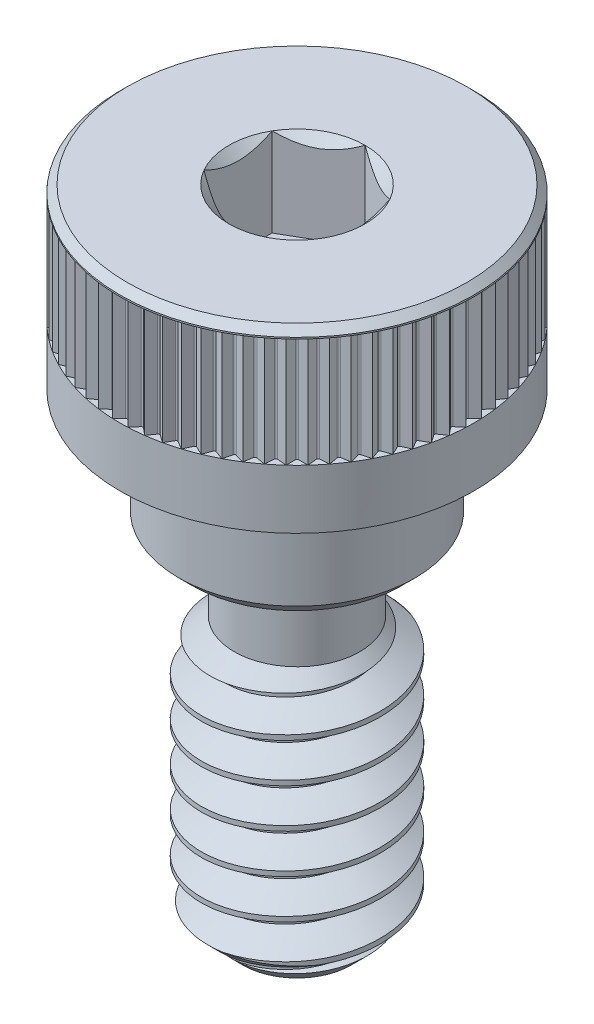
SolidWorks part; units mm, degrees
ref_plane "Front" through (0, 0, 0) normal (0, 0, 1) x (1, 0, 0)
ref_plane "Top" through (0, 0, 0) normal (0, 1, 0) x (1, 0, 0)
ref_plane "Right" through (0, 0, 0) normal (1, 0, 0) x (0, 0, -1)
sketch "Sketch1" plane through (0, 0, 0) normal (0, 1, 0) x (1, 0, 0)
  circle A0 centre (0, 0) radius 4.7625
  point P3 (0, -4.7625)
  dimension "Head Dia" = 9.525
extrude "Extrude1" add sketch "Sketch1" along normal blind 4.7625
sketch "Sketch2" plane through (0, 4.7625, 0) normal (0, 1, 0) x (-1, 0, 0)
  line L1 (0, -1.8331) -> (1.5875, -0.9165)
  line L2 (1.5875, -0.9165) -> (1.5875, 0.9165)
  line L3 (1.5875, 0.9165) -> (0, 1.8331)
  line L4 (0, 1.8331) -> (-1.5875, 0.9165)
  line L5 (-1.5875, 0.9165) -> (-1.5875, -0.9165)
  line L6 (-1.5875, -0.9165) -> (0, -1.8331)
  circle A0 centre (0, 0) radius 1.5875 construction
  circle A1 centre (0, 0) radius 4.7625 construction
  dimension "Hex Key" = 3.175
extrude "Cut-Extrude1" cut sketch "Sketch2" against normal blind 2.3813
sketch "Sketch4" plane through (0, 0, 0) normal (0, -1, 0) x (1, 0, 0)
  circle A0 centre (0, 0) radius 3.175
  circle A1 centre (0, 0) radius 4.7625 construction
  dimension "Shoulder Dia" = 6.35
extrude "Extrude2" add sketch "Sketch4" along normal blind 3.175
sketch "Sketch5" plane through (0, -3.175, 0) normal (0, -1, 0) x (1, 0, 0)
  circle A0 centre (0, 0) radius 2.413
  circle A1 centre (0, 0) radius 3.175 construction
  dimension "Thread Dia" = 4.826
extrude "Extrude3" add sketch "Sketch5" along normal blind 9.525
chamfer "Chamfer1" distance 0.9525 angle 45 1 edges at (0, -12.7, -2.413)
sketch "Sketch12" plane through (0, -12.7, 0) normal (0, -1, 0) x (1, 0, 0)
  circle A0 centre (0, 0) radius 2.413
  circle A1 centre (0, 0) radius 2.413 construction
curve "Helix/Spiral1" pitch 1.0583 height 9.525 turns 9 parameters "Thread Pitch "=1.0583
sketch "Sketch13" plane through (0, 0, 0) normal (0, 0, 1) x (1, 0, 0)
  line L0 (2.413, -12.7) -> (2.413, -13.626)
  line L1 (2.413, -13.626) -> (1.7256, -13.2292)
  line L2 (1.7256, -13.2292) -> (1.7256, -13.0969)
  line L3 (1.7256, -13.0969) -> (2.413, -12.7)
  line L4 (2.413, -13.163) -> (1.7256, -13.163) construction
  line L5 (2.413, -11.7475) -> (2.413, -3.175) construction
  line L6 (2.0693, -12.8984) -> (2.0693, -13.4276) construction
  line L7 (-1.4605, -12.7) -> (1.4605, -12.7) construction
  dimension "D1" = 60
  dimension "D2" = 0.1323
  dimension "D3" = 0.5292
sweep "Cut-Sweep1" cut profiles "Sketch13" path "Helix/Spiral1"
sketch "Sketch18" plane through (0, 0, 0) normal (0, 0, 1) x (1, 0, 0)
  line L0 (2.413, -3.175) -> (1.6891, -3.175)
  line L1 (1.6891, -3.175) -> (1.6891, -5.2832)
  line L2 (1.6891, -5.2832) -> (2.413, -6.0071)
  line L3 (2.413, -6.0071) -> (2.413, -3.175)
  line L4 (-3.175, -3.175) -> (3.175, -3.175) construction
  line L5 (0, 0) -> (0, -10.8393) construction
  dimension "D1" = 45
  dimension "B" = 2.1082
  dimension "A" = 3.3782
revolve "Cut-Revolve1" cut sketch "Sketch18" angle 360 about axis through (0, -3.175, 0) along (0, 1, 0)
ref_plane "Plane1" through (0, 1.5875, 0) normal (0, 1, 0) x (-1, 0, 0)
sketch "Sketch10" plane through (0, 1.5875, 0) normal (0, 1, 0) x (-1, 0, 0)
  line L0 (0, 0) -> (-4.5683, 0) construction
  line L1 (0, 0) -> (-11.9081, -0.5199) construction
  line L2 (-4.758, -0.2077) -> (-4.8277, -0.2108)
  line L3 (-4.758, -0.2077) -> (-4.581, -0.0308)
  line L4 (0, 0) -> (-11.9081, 0.5199) construction
  line L5 (-4.581, 0.0308) -> (-4.758, 0.2077)
  line L6 (-4.8277, -0.2108) -> (-4.8277, 0.2108)
  line L7 (-4.8277, 0.2108) -> (-4.758, 0.2077)
  circle A0 centre (0, 0) radius 4.7625 construction
  arc A2 (-4.581, -0.0308) -> (-4.581, 0.0308) centre (-4.6118, 0) ccw
  point P3 (-4.7625, 0)
  dimension "D4" = 0.0435
  dimension "D1" = 90
  dimension "D2" = 5
  dimension "D3" = 0.0697
  dimension "D5" = 0.1942
extrude "Cut-Extrude3" cut sketch "Sketch10" along normal offset from surface (2.9419 mm away) 0.2331 up to face at (0, 4.7625, 0)
chamfer "Chamfer2" distance 0.1942 angle 45 1 edges at (0, 4.7625, 4.7625)
pattern_circular "CirPattern2" count 72 over 360 about axis through (0, 0, 0) along (0, 1, 0) of "Cut-Extrude3"
sketch "Sketch14" plane through (0, 4.7625, 0) normal (0, 1, 0) x (1, 0, 0)
  circle A0 centre (0, 0) radius 4.7625
  arc A1 (-1.4321, 4.5421) -> (-4.5421, -1.4321) centre (0, 0) ccw construction
sketch "Sketch15" plane through (0, 0, 0) normal (1, 0, 0) x (0, 0, -1)
  line L0 (-2.413, -3.175) -> (-2.413, -12.7)
  line L1 (2.413, -12.7) -> (2.413, -3.175)
  line L2 (-3.175, -3.175) -> (3.175, -3.175) construction
  point P7 (-2.413, -8.7312)
  point P9 (2.413, -8.7312)
  point P10 (-2.413, -5.2832)
  point P11 (2.413, -5.2832)
  dimension "D1" = 3.9688
sketch "Sketch16" plane through (0, 0, 0) normal (1, 0, 0) x (0, 0, -1)
  line L0 (-3.175, 0) -> (-3.175, -3.175)
  line L1 (3.175, 0) -> (3.175, -3.175)
  dimension "Shoulder Length" = 3.175
sketch "Sketch17" plane through (0, -3.175, 0) normal (0, -1, 0) x (1, 0, 0)
  circle A0 centre (0, 0) radius 3.175
  circle A1 centre (0, 0) radius 3.175 construction
  dimension "Shoulder Dia" = 6.35
fillet "Fillet1" radius 0.5292 1 edges at (0, -3.175, -1.6891)
chamfer "Chamfer3" distance 0.3528 angle 45 1 edges at (0, -3.175, -3.175)
sketch "Sketch19" plane through (0, 4.7625, 0) normal (0, 1, 0) x (1, 0, 0)
  circle A0 centre (0, 0) radius 1.8331
extrude "Extrude4" cut sketch "Sketch19" against normal through all draft 45
equation "\"D1@Cut-Extrude1\"=\"Head Ht@Extrude1\"/2"
equation "\"D1@Chamfer1\" = \"Thread Length@Extrude3\" * .1"
equation "\"D3@Helix/Spiral1\" = \"Thread Length@Extrude3\""
equation "\"D2@Sketch13\" = \"Thread Pitch @Helix/Spiral1\" * .125"
equation "\"D3@Sketch13\" = \"Thread Pitch @Helix/Spiral1\" * .5"
equation "\"D3@Sketch10\" = \"Head Dia@Sketch1\" * .0073205143"
equation "\"D4@Sketch10\" = \"Head Dia@Sketch1\" * .0045714286"
equation "\"Shoulder Length@Sketch16\" = \"Shoulder Length@Extrude2\""
equation "\"Shoulder Dia@Sketch17\" = \"Shoulder Dia@Sketch4\""
equation "\"D1@Plane1\" = \"Head Ht@Extrude1\"*2/3"
equation "\"D1@Chamfer2\" = \"D5@Sketch10\""
equation "\"D1@Cut-Extrude3\"=\"D5@Sketch10\"*1.2"
equation "\"D1@Fillet1\" = \"Thread Pitch @Helix/Spiral1\"*.50"
equation "\"D1@Chamfer3\" = \"Thread Pitch @Helix/Spiral1\"/3"
equation "\"D1@Sketch15\" = \"Thread Pitch @Helix/Spiral1\"*3.7500"
